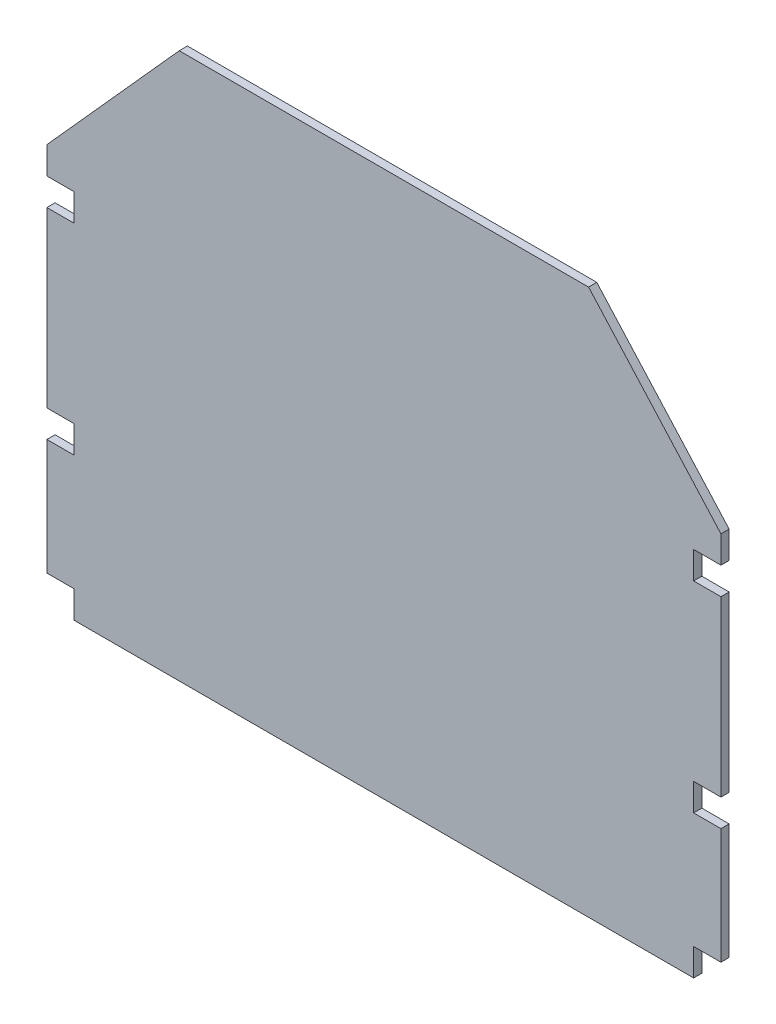
SolidWorks part; units mm, degrees
ref_plane "Plan de face" through (0, 0, 0) normal (0, 0, 1) x (1, 0, 0)
ref_plane "Plan de dessus" through (0, 0, 0) normal (0, 1, 0) x (1, 0, 0)
ref_plane "Plan de droite" through (0, 0, 0) normal (1, 0, 0) x (0, 0, -1)
sketch "Esquisse1" plane through (0, 0, 0) normal (0, 0, 1) x (1, 0, 0)
  line L0 (0, 0) -> (280.2, 0) construction
  line L1 (280.2, 0) -> (280.2, 127.45) construction
  line L2 (280.2, 127.45) -> (215.1, 200) construction
  line L3 (215.1, 200) -> (65.1, 200) construction
  line L4 (65.1, 200) -> (0, 127.45) construction
  line L5 (0, 0) -> (0, 127.45) construction
  line L6 (0, 0) -> (0, 127.45)
  line L7 (0, 127.45) -> (65.1, 200)
  line L8 (65.1, 200) -> (215.1, 200)
  line L9 (215.1, 200) -> (280.2, 127.45)
  line L10 (280.2, 127.45) -> (280.2, 0)
  line L11 (280.2, 0) -> (0, 0)
  point P3 (140.1, 200)
  point P8 (140.1, 0)
  dimension "D1" = 280.2
  dimension "D2" = 200
  dimension "D3" = 127.45
  dimension "D4" = 127.45
  dimension "D5" = 150
extrude "Boss.-Extru.1" add sketch "Esquisse1" along normal blind 3
sketch "Esquisse2" plane through (0, 0, 0) normal (0, 0, -1) x (-1, 0, 0)
  line L1 (-16.6, 252) -> (-16.6, 0) construction
  line L2 (-16.6, 0) -> (-16.6, 145.9694)
  line L3 (-16.6, 0) -> (0, 0)
  line L4 (0, 0) -> (0, 127.45)
  line L5 (0, 127.45) -> (-16.6, 145.9694)
  line L6 (-140.1, 200) -> (-140.1, -18.7191) construction
  line L7 (-215.1, 200) -> (-65.1, 200) construction
  line L8 (-280.2, 127.45) -> (-263.6, 145.9694)
  line L9 (-280.2, 0) -> (-280.2, 127.45)
  line L10 (-263.6, 0) -> (-280.2, 0)
  line L11 (-263.6, 0) -> (-263.6, 145.9694)
extrude "Enlèv. mat.-Extru.1" cut sketch "Esquisse2" against normal through all
sketch "Esquisse4" plane through (0, 0, 3) normal (0, 0, 1) x (1, 0, 0)
  line L0 (140.1, 200) -> (140.1, -14.9568) construction
  line L1 (215.1, 200) -> (65.1, 200) construction
  line L2 (16.6, 145.9497) -> (16.6, 0) construction
  line L3 (16.6, 0) -> (26.6, 0)
  line L4 (16.6, 0) -> (16.6, 10)
  line L5 (16.6, 10) -> (26.6, 10)
  line L6 (26.6, 0) -> (26.6, 10)
  line L7 (16.6, 52.4) -> (26.6, 52.4)
  line L8 (16.6, 52.4) -> (16.6, 62.4)
  line L9 (16.6, 62.4) -> (26.6, 62.4)
  line L10 (26.6, 52.4) -> (26.6, 62.4)
  line L11 (253.6, 126) -> (253.6, 136)
  line L12 (16.6, 126) -> (26.6, 126)
  line L13 (16.6, 126) -> (16.6, 136)
  line L14 (16.6, 136) -> (26.6, 136)
  line L15 (26.6, 126) -> (26.6, 136)
  line L16 (263.6, 136) -> (253.6, 136)
  line L17 (263.6, 126) -> (263.6, 136)
  line L18 (263.6, 126) -> (253.6, 126)
  line L19 (253.6, 52.4) -> (253.6, 62.4)
  line L20 (263.6, 62.4) -> (253.6, 62.4)
  line L21 (263.6, 52.4) -> (263.6, 62.4)
  line L22 (263.6, 52.4) -> (253.6, 52.4)
  line L23 (253.6, 0) -> (253.6, 10)
  line L24 (263.6, 10) -> (253.6, 10)
  line L25 (263.6, 0) -> (263.6, 10)
  line L26 (263.6, 0) -> (253.6, 0)
  point P19 (21.6, 62.4)
  dimension "D1" = 10
  dimension "D2" = 10
  dimension "D3" = 10
  dimension "D4" = 10
  dimension "D5" = 10
  dimension "D6" = 10
  dimension "D7" = 42.4
  dimension "D8" = 63.6
extrude "Enlèv. mat.-Extru.2" cut sketch "Esquisse4" against normal through all
